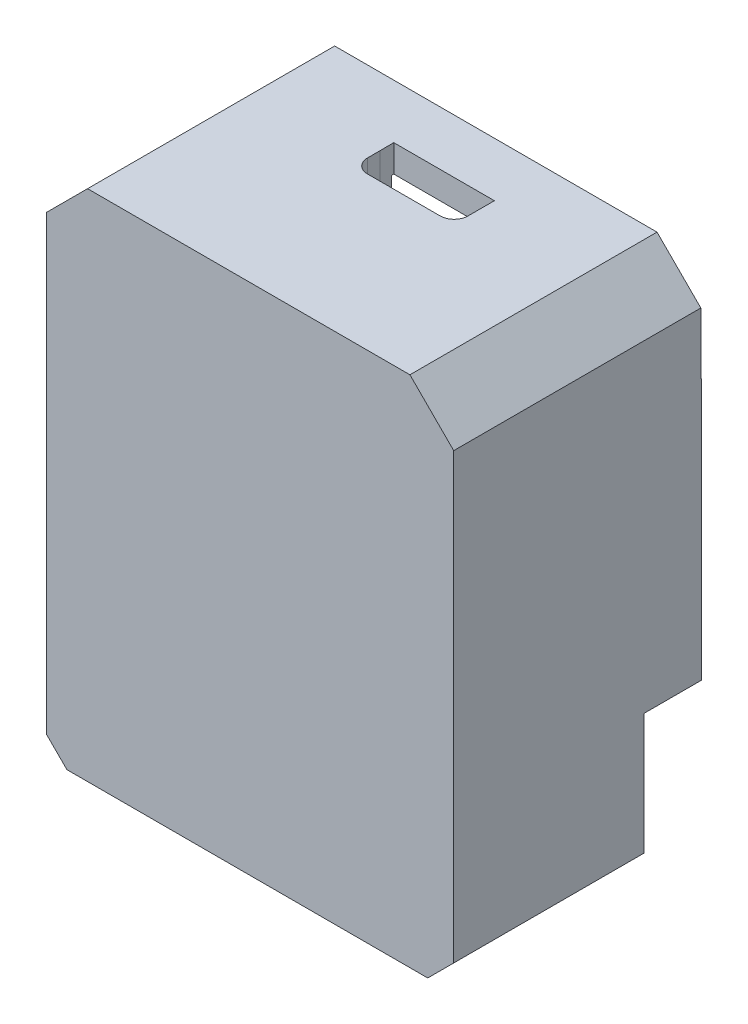
SolidWorks part; units mm, degrees
ref_plane "前视基准面" through (0, 0, 0) normal (0, 0, 1) x (1, 0, 0)
ref_plane "上视基准面" through (0, 0, 0) normal (0, 1, 0) x (1, 0, 0)
ref_plane "右视基准面" through (0, 0, 0) normal (1, 0, 0) x (0, 0, -1)
sketch "草图1" plane through (0, 0, 0) normal (0, 0, 1) x (1, 0, 0)
  line L0 (-5.5542, -29.1173) -> (6.8242, -29.1173)
  line L28 (5.6812, -27.9743) -> (6.8242, -29.1173)
  line L29 (6.8242, -29.1173) -> (15.7818, -29.1173)
  line L30 (15.7818, -29.1173) -> (20.1003, -24.7989)
  line L31 (20.1003, -24.7989) -> (20.1003, 9.906)
  line L32 (20.1003, 9.906) -> (20.1003, 13.6228)
  line L33 (20.1003, 13.6228) -> (15.0198, 18.7033)
  line L34 (15.0198, 18.7033) -> (-15.4008, 18.7033)
  line L35 (-15.4008, 18.7033) -> (-20.2273, 13.8768)
  line L36 (-20.2273, 13.8768) -> (-20.2273, -25.3069)
  line L37 (-20.2273, -25.3069) -> (-16.4168, -29.1173)
  line L38 (-16.4168, -29.1173) -> (-5.5542, -29.1173)
  line L39 (-5.5542, -29.1173) -> (-4.4112, -27.9743)
  line L40 (-4.4112, -27.9743) -> (5.6812, -27.9743)
  line L41 (5.6812, -27.9743) -> (6.8242, -29.1173)
  line L42 (6.8242, -29.1173) -> (15.7818, -29.1173)
  line L43 (15.7818, -29.1173) -> (18.1003, -26.7989)
  line L50 (-18.2273, -27.3069) -> (-16.4168, -29.1173)
  line L51 (-16.4168, -29.1173) -> (-5.5542, -29.1173)
  line L52 (-5.5542, -29.1173) -> (-4.4112, -27.9743)
  line L53 (-4.4112, -27.9743) -> (5.6812, -27.9743)
  line L67 (-18.2273, -24.4784) -> (-18.2273, -27.3069)
  line L68 (18.1003, -23.9704) -> (18.1003, -26.7989)
  line L69 (-0.1905, 16.7033) -> (-0.1905, -49983.2967) construction
  line L70 (14.8095, -26.7989) -> (-15.1905, -26.7989)
  line L71 (-16.1905, -25.7989) -> (-16.1905, 11.2011)
  line L72 (-15.1905, 12.2011) -> (14.8095, 12.2011)
  line L73 (15.8095, -25.7989) -> (15.8095, 11.2011)
  line L81 (-5.2396, -25.9743) -> (6.5096, -25.9743)
  line L82 (-6.3826, -27.1173) -> (-5.2396, -25.9743)
  line L83 (-15.5884, -27.1173) -> (-6.3826, -27.1173)
  line L84 (-18.2273, -24.4784) -> (-15.5884, -27.1173)
  line L85 (-18.2273, 13.0484) -> (-18.2273, -24.4784)
  line L86 (-14.5724, 16.7033) -> (-18.2273, 13.0484)
  line L87 (14.1914, 16.7033) -> (-14.5724, 16.7033)
  line L88 (18.1003, 12.7944) -> (14.1914, 16.7033)
  line L89 (18.1003, 9.906) -> (18.1003, 12.7944)
  line L90 (18.1003, -23.9704) -> (18.1003, 9.906)
  line L91 (14.9534, -27.1173) -> (18.1003, -23.9704)
  line L92 (7.6526, -27.1173) -> (14.9534, -27.1173)
  line L93 (6.5096, -25.9743) -> (7.6526, -27.1173)
  line L98 (-18.2273, 13.0484) -> (-18.2273, -24.4784)
  line L99 (-14.5724, 16.7033) -> (-18.2273, 13.0484)
  line L100 (14.1914, 16.7033) -> (-14.5724, 16.7033)
  line L101 (18.1003, 12.7944) -> (14.1914, 16.7033)
  line L102 (18.1003, 9.906) -> (18.1003, 12.7944)
  line L103 (18.1003, -23.9704) -> (18.1003, 9.906)
  arc A2 (-15.1905, -26.7989) -> (-16.1905, -25.7989) centre (-15.1905, -25.7989) cw
  arc A3 (15.8095, -25.7989) -> (14.8095, -26.7989) centre (14.8095, -25.7989) cw
  arc A4 (15.8095, 11.2011) -> (14.8095, 12.2011) centre (14.8095, 11.2011) ccw
  arc A5 (-16.1905, 11.2011) -> (-15.1905, 12.2011) centre (-15.1905, 11.2011) cw
  point P4 (-0.1905, 16.7033)
  point P13 (-0.1905, -26.7989)
  point P15 (-0.1905, 12.2011)
  point P19 (-16.1905, -26.7989)
  point P24 (15.8095, -26.7989)
  point P29 (15.8095, 12.2011)
  point P37 (-16.1905, 12.2011)
  dimension "D5" = 1
  dimension "D3" = 16
  dimension "D4" = 39
  dimension "D1" = 5
  dimension "D2" = 3
extrude "凸台-拉伸1" add sketch "草图1" along normal blind 15 contours L69 L100 L99 L98 L67 L50 L51 L52 L53 L70 A2 L71 A5 L72 | L69 L53 L52 L0 | L53 L69 L0 L41 | L100 L69 L72 A4 L73 A3 L70 L53 L41 L42 L43 L68 L103 L102 L101 region at (-2.598, -28.5686, 0) region at (-10.3506, -27.7713, 0) region at (3.0396, -28.5627, 0) region at (10.3748, -27.6201, 0) region at (-17.7535, -5.715, 0) region at (11.0718, -26.8463, 0)
sketch "草图2" plane through (0, 0, 15) normal (0, 0, 1) x (1, 0, 0)
  line L0 (-16.4168, -29.1173) -> (15.7818, -29.1173) construction
  line L24 (-18.2273, 13.0484) -> (-18.2273, -27.3069)
  line L25 (-18.2273, -27.3069) -> (-16.4168, -29.1173)
  line L26 (-16.4168, -29.1173) -> (-0.3175, -29.1173)
  line L30 (-0.3175, -29.1173) -> (15.7818, -29.1173)
  line L31 (15.7818, -29.1173) -> (18.1003, -26.7989)
  line L32 (18.1003, -26.7989) -> (18.1003, 12.7944)
  line L33 (18.1003, 12.7944) -> (14.1914, 16.7033)
  line L34 (14.1914, 16.7033) -> (-14.5724, 16.7033)
  line L35 (-14.5724, 16.7033) -> (-18.2273, 13.0484)
  point P2 (6.6282, -29.1173)
  point P4 (-0.3175, -29.1173)
  dimension "D1" = 39.5933
extrude "凸台-拉伸2" add sketch "草图2" along normal blind 2 contours L34 L35 L24 L25 L26 L30 L31 L32 L33 region at (-0.0839, -6.337, 15)
sketch "草图3" plane through (-16.1905, 0, 0) normal (1, 0, 0) x (0, 0, -1)
  line L0 (0, 11.2011) -> (0, 9.2011)
  line L2 (0, 9.2011) -> (-2, 9.2011)
  line L3 (-2, 9.2011) -> (-2, -20.7989)
  line L4 (-2, -20.7989) -> (0, -20.7989)
  line L5 (0, -20.7989) -> (0, 9.2011)
  dimension "D1" = 2
  dimension "D2" = 2
  dimension "D3" = 30
  dimension "D4" = 2
extrude "凸台-拉伸3" add sketch "草图3" along normal blind 2 contours L3 L4 L2 region at (-16.1905, -5.7989, 1)
sketch "草图4" plane through (15.8095, 0, 0) normal (-1, 0, 0) x (0, 0, 1)
  line L4 (2, -20.7989) -> (2, 9.2011)
  line L5 (0, -20.7989) -> (2, -20.7989)
  line L6 (0, 9.2011) -> (0, -20.7989)
  line L7 (2, 9.2011) -> (0, 9.2011)
  line L8 (2, -20.7989) -> (2, 9.2011)
  line L9 (0, -20.7989) -> (2, -20.7989)
  line L11 (2, 9.2011) -> (0, 9.2011)
  line L12 (0, 9.2011) -> (0, -20.7989)
  dimension "D1" = 0
extrude "凸台-拉伸4" add sketch "草图4" along normal blind 2
sketch "草图5" plane through (0, 0, 0) normal (1, 0, 0) x (0, 0, -1)
  line L0 (0, 15.3533) -> (3.1001, 15.3533)
  line L1 (2.1001, 13.7033) -> (2.1001, 12.7033)
  line L3 (2.1001, 12.7033) -> (3.1001, 12.7033)
  line L5 (3.1001, 12.7033) -> (3.1001, 15.3533)
  line L6 (2.1001, 13.7033) -> (2.1001, 14.0033)
  line L7 (2.1001, 14.0033) -> (0, 14.0033)
  line L9 (0, 14.0033) -> (0, 15.3533)
  dimension "D1" = 2.65
  dimension "D2" = 1
  dimension "D3" = 1
  dimension "D4" = 0.3
  dimension "D5" = 3.1001
extrude "凸台-拉伸5" add sketch "草图5" along normal blind 5.5 from offset 7 contours L9 L7 L6 L1 L3 L5 L0 region at (0, 14.3643, -1.7989)
mirror "镜向1" about plane through (0, 0, 0) normal (1, 0, 0) of "凸台-拉伸5"
sketch "草图7" plane through (0, 0, 0) normal (0, 1, 0) x (1, 0, 0)
  line L0 (-18.2273, 0) -> (-18.2273, 3.1)
  line L3 (-15.2273, 2.1001) -> (-11.2273, 2.1001)
  line L4 (-11.2273, 2.1001) -> (-11.2273, 3.1)
  line L5 (-11.2273, 3.1) -> (-16.2273, 3.1)
  line L7 (-15.4773, 0) -> (-18.2273, 0)
  line L8 (-15.2273, 2.1001) -> (-15.4773, 2.1001)
  line L9 (-15.4773, 2.1001) -> (-15.4773, 0)
  line L10 (-18.2273, 3.1) -> (-18.2273, 4.1)
  line L11 (-16.2273, 4.1) -> (-11.2273, 4.1)
  line L12 (-11.2273, 4.1) -> (-11.2273, 5.1)
  line L13 (-11.2273, 5.1) -> (-18.2273, 5.1)
  line L14 (-18.2273, 5.1) -> (-18.2273, 4.1)
  line L16 (-16.2273, 3.1) -> (-16.2273, 4.1)
  line L17 (0, 0) -> (0, -7.2854) construction
  dimension "D1" = 1
  dimension "D2" = 4
  dimension "D3" = 3.1
  dimension "D4" = 0.25
  dimension "D5" = 1
  dimension "D6" = 2
extrude "凸台-拉伸6" add sketch "草图7" against normal blind 16 and the other way blind 7.3 contours L5 L16 L11 L12 L13 L14 L10 L0 L7 L9 L8 L3 L4 region at (-15.5205, 0, -2.9237)
sketch "草图10" plane through (0, -16, 0) normal (0, -1, 0) x (1, 0, 0)
  line L0 (16.2277, -3.1) -> (11.2273, -3.1)
  line L1 (11.2273, -3.1) -> (11.2273, -2.0481)
  line L2 (15.6003, -1.6001) -> (15.6003, 0)
  line L3 (12.3185, -2.0481) -> (9.5255, -2.0481) construction
  line L4 (11.2273, -2.0481) -> (15.6003, -2.0481)
  line L5 (16.2277, -3.1) -> (16.2281, -4.1)
  line L6 (18.1003, 0) -> (18.1003, -5.1)
  line L7 (15.6003, -1.6001) -> (15.6003, -2.0481)
  line L9 (15.6003, 0) -> (16.2266, 0.0019)
  line L15 (16.2281, -4.1) -> (11.2273, -4.1)
  line L16 (11.2273, -4.1) -> (11.2273, -5.1)
  line L17 (11.2273, -5.1) -> (18.1003, -5.1)
  line L20 (18.1003, 0) -> (16.2266, 0.0019)
  dimension "D2" = 1.0519
  dimension "D3" = 5.1
  dimension "D1" = 6.873
  dimension "D5" = 1
  dimension "D7" = 1
extrude "凸台-拉伸7" add sketch "草图10" against normal blind 23.3
sketch "草图11" plane through (0, 0, 0) normal (0, 0, -1) x (-1, 0, 0)
  line L3 (-15.2203, 7.1241) -> (-18.1003, 7.1241)
  line L11 (15.3473, 7.1241) -> (18.2273, 7.1241)
  line L12 (15.3473, 11.8555) -> (15.3473, 7.1241)
  line L13 (15.3473, 11.8555) -> (13.4146, 13.7882)
  line L14 (13.4146, 13.7882) -> (12.9307, 14.2721)
  line L15 (-12.5497, 14.2721) -> (12.9307, 14.2721)
  line L16 (-15.2203, 11.6015) -> (-12.5497, 14.2721)
  line L17 (-15.2203, 11.6015) -> (-15.2203, 7.1241)
  line L85 (-18.1003, 12.7944) -> (-18.1003, 7.1241)
  line L89 (18.2273, 7.1241) -> (18.2273, 13.0484)
  line L109 (18.2273, 13.0484) -> (14.5724, 16.7033)
  line L111 (14.5724, 16.7033) -> (-14.1914, 16.7033)
  line L113 (-14.1914, 16.7033) -> (-18.1003, 12.7944)
  point P2 (0, 0)
  point P4 (0, 0)
  point P8 (18.2273, 7.1595)
  point P18 (-18.1003, 7.1591)
extrude "凸台-拉伸9" add sketch "草图11" along normal blind 5.05
sketch "草图14" plane through (0, 16.7033, 0) normal (0, 1, 0) x (1, 0, 0)
  line L13 (-3.2225, -3.0756) -> (3.2733, -3.0756)
  line L14 (-987.0512, 0.8) -> (49012.9488, 0.8) construction
  line L15 (-4.1585, -1.0164) -> (-4.1585, -2.1396)
  line L16 (3.2733, -0.0804) -> (-3.2225, -0.0804)
  line L17 (4.2093, -2.1396) -> (4.2093, -1.0164)
  line L18 (-3.2225, -3.3756) -> (3.2733, -3.3756)
  line L19 (-4.4585, -1.0164) -> (-4.4585, -2.1396)
  line L20 (3.2733, 0.2196) -> (-3.2225, 0.2196)
  line L21 (4.5093, -2.1396) -> (4.5093, -1.0164)
  line L22 (4.5093, -1.0164) -> (4.5093, 0.2196)
  line L23 (4.5093, 0.2196) -> (3.2733, 0.2196)
  line L24 (-4.4585, -1.0164) -> (-4.4705, 0.2196)
  line L25 (-4.4705, 0) -> (-4.4705, 1.6001) construction
  line L26 (-4.4705, 0.2196) -> (-3.2225, 0.2196)
  arc A12 (4.2093, -2.1396) -> (3.2733, -3.0756) centre (3.2733, -2.1396) cw
  arc A13 (-3.2225, -3.0756) -> (-4.1585, -2.1396) centre (-3.2225, -2.1396) cw
  arc A14 (-4.1585, -1.0164) -> (-3.2225, -0.0804) centre (-3.2225, -1.0164) cw
  arc A15 (3.2733, -0.0804) -> (4.2093, -1.0164) centre (3.2733, -1.0164) cw
  arc A16 (4.5093, -2.1396) -> (3.2733, -3.3756) centre (3.2733, -2.1396) cw
  arc A17 (-3.2225, -3.3756) -> (-4.4585, -2.1396) centre (-3.2225, -2.1396) cw
  arc A18 (-4.4585, -1.0164) -> (-3.2225, 0.2196) centre (-3.2225, -1.0164) cw
  arc A19 (3.2733, 0.2196) -> (4.5093, -1.0164) centre (3.2733, -1.0164) cw
  dimension "D1" = 0.3
extrude "切除-拉伸3" cut sketch "草图14" against normal blind 8.15 contours A15 L16 A14 L15 A13 L13 A12 L17 | A19 L20 A18 L19 A17 L18 A16 L21 L16 A15 L17 A12 L13 A13 L15 A14 | L23 A19 L22 | L24 A18 L26 region at (0.0254, 16.7033, 1.578) region at (-4.0282, 16.7033, 2.9452) region at (-4.1886, 16.7033, 0.0595) region at (4.2332, 16.7033, 0.0565)
